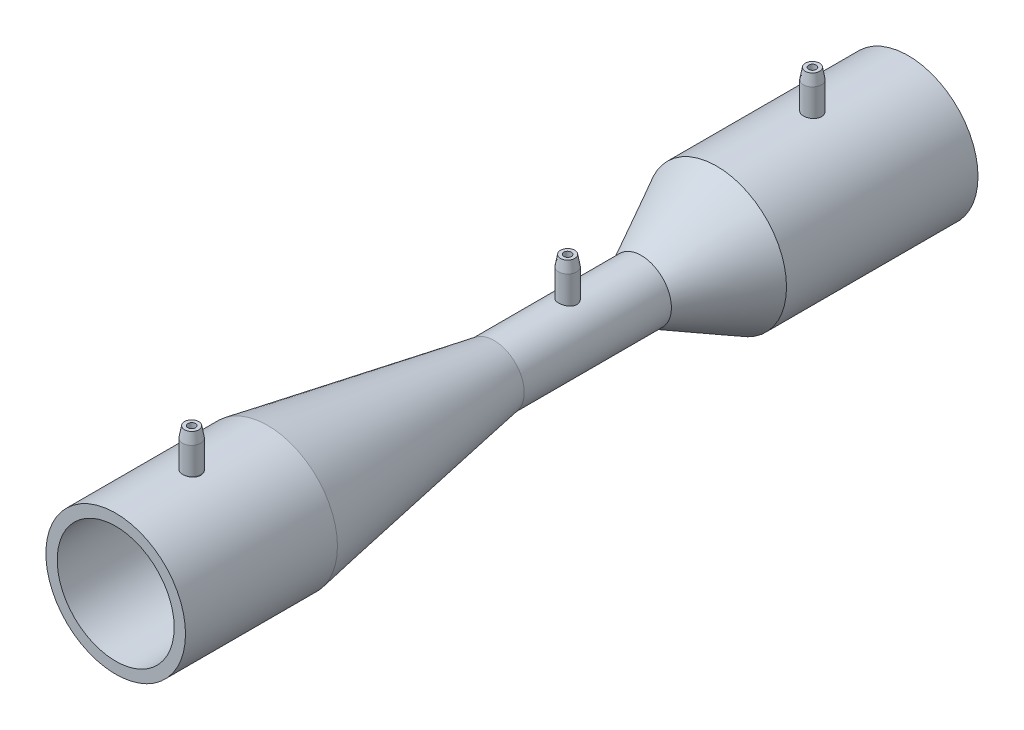
SolidWorks part; units mm, degrees
ref_plane "Front Plane" through (0, 0, 0) normal (0, 0, 1) x (1, 0, 0)
ref_plane "Top Plane" through (0, 0, 0) normal (0, 1, 0) x (1, 0, 0)
ref_plane "Right Plane" through (0, 0, 0) normal (1, 0, 0) x (0, 0, -1)
sketch "Sketch1" plane through (0, 0, 0) normal (1, 0, 0) x (0, 0, -1)
  line L0 (77.8723, 0) -> (-77.8723, 0) construction
  line L1 (-135.6286, 15.5) -> (77.8723, 15.5) construction
  line L2 (-135.6286, 15.5) -> (-95.6286, 15.5)
  line L3 (-95.6286, 15.5) -> (-35.6286, 5)
  line L4 (-35.6286, 5) -> (4.3714, 5)
  line L5 (4.3714, 5) -> (24.3714, 15.5)
  line L6 (24.3714, 15.5) -> (74.3714, 15.5)
  line L7 (-76.7205, 5) -> (45.4632, 5) construction
  line L8 (-135.6286, 18.5) -> (-95.3681, 18.5)
  line L9 (-95.3681, 18.5) -> (-35.3681, 8)
  line L10 (-35.3681, 8) -> (3.6317, 8)
  line L11 (3.6317, 8) -> (23.6317, 18.5)
  line L12 (23.6317, 18.5) -> (74.3714, 18.5)
  line L13 (-135.6286, 15.5) -> (-135.6286, 18.5)
  line L14 (74.3714, 15.5) -> (74.3714, 18.5)
  point P4 (0, 0)
  point P15 (-15.6286, 5)
  dimension "D1" = 15.5
  dimension "D2" = 40
  dimension "D3" = 60
  dimension "D4" = 40
  dimension "D5" = 20
  dimension "D6" = 50
  dimension "D7" = 15.5
  dimension "D8" = 5
  dimension "D9" = 3
revolve "Revolve1" add sketch "Sketch1" angle 360 about L0 reverse direction yes
sketch "Sketch2" plane through (0, 0, 0) normal (1, 0, 0) x (0, 0, -1)
  line L0 (-115.4984, 18.5) -> (-115.4984, 28.5)
  line L2 (-15.8682, 8) -> (-15.8682, 18)
  line L3 (-35.3681, 8) -> (3.6317, 8) construction
  line L4 (49.0016, 18.5) -> (49.0016, 28.5)
  line L5 (23.6317, 18.5) -> (74.3714, 18.5) construction
  line L6 (-95.3681, 18.5) -> (-135.6286, 18.5) construction
  line L7 (-14.8682, 5) -> (-14.8682, 18)
  line L8 (50.0016, 15.5) -> (50.0016, 28.5)
  line L9 (-114.4984, 18.5) -> (-114.4984, 28.5)
  line L10 (-16.8682, 5) -> (-16.8682, 18)
  line L11 (48.0016, 15.5) -> (48.0016, 28.5)
  line L13 (-13.4832, 5) -> (-13.4832, 18)
  line L14 (51.3866, 15.5) -> (51.3866, 28.5)
  line L16 (-18.2532, 5) -> (-18.2532, 18)
  line L17 (46.6166, 15.5) -> (46.6166, 28.5)
  line L19 (-18.2532, 18) -> (-13.4832, 18)
  line L20 (46.6166, 28.5) -> (51.3866, 28.5)
  line L25 (-135.6286, 15.5) -> (-95.6286, 15.5) construction
  line L26 (-116.4984, 18.5) -> (-116.4984, 28.5)
  line L27 (-113.1084, 18.5) -> (-113.1084, 28.5)
  line L28 (-117.8884, 18.5) -> (-117.8884, 28.5)
  line L29 (-18.2532, 8) -> (-18.2532, 18) construction
  line L30 (-35.6286, 5) -> (4.3714, 5) construction
  line L31 (-16.8682, 8) -> (-16.8682, 18) construction
  line L32 (-14.8682, 8) -> (-14.8682, 18) construction
  line L33 (-13.4832, 8) -> (-13.4832, 18) construction
  line L34 (46.6166, 18.5) -> (46.6166, 28.5) construction
  line L35 (24.3714, 15.5) -> (74.3714, 15.5) construction
  line L36 (48.0016, 18.5) -> (48.0016, 28.5) construction
  line L37 (50.0016, 18.5) -> (50.0016, 28.5) construction
  line L38 (51.3866, 18.5) -> (51.3866, 28.5) construction
  line L39 (46.6166, 15.5) -> (51.3866, 15.5)
  line L40 (-18.2532, 5) -> (-13.4832, 5)
  line L41 (-117.8834, 15.5) -> (-113.1134, 15.5)
  line L42 (-117.8884, 18.5) -> (-117.8834, 15.5)
  line L43 (-116.4984, 18.5) -> (-116.4984, 15.5)
  line L44 (-116.4984, 15.5) -> (-114.4984, 15.5)
  line L45 (-114.4984, 15.5) -> (-114.4984, 18.5)
  line L46 (-113.1134, 15.5) -> (-113.1084, 18.5)
  line L47 (-115.4984, 18.5) -> (-115.4984, 15.5)
  line L48 (-117.8884, 28.5) -> (-113.1084, 28.5)
  dimension "D2" = 10
  dimension "D3" = 10
  dimension "D1" = 10
  dimension "D4" = 1
  dimension "D6" = 2.39
  dimension "D7" = 2.39
revolve "Revolve2" add sketch "Sketch2" angle 360 about L0 region at (0, 22.0023, 113.8037)
revolve "Revolve3" add sketch "Sketch2<5>" angle 360 about L2 region at (0, 11.5, 14.1757)
sketch "Sketch2<5>" plane through (0, 0, 0) normal (1, 0, 0) x (0, 0, -1) same geometry as "Sketch2"
revolve "Revolve4" add sketch "Sketch2<6>" angle 360 about L4 region at (0, 22, -50.6941)
sketch "Sketch2<6>" plane through (0, 0, 0) normal (1, 0, 0) x (0, 0, -1) same geometry as "Sketch2"
chamfer "Chamfer1" distance 0.5 angle 80 1 edges at (0, 28.5, 113.1084) first distance on face at (0, 28.5, 113.1084)
chamfer "Chamfer2" distance 0.5 angle 80 1 edges at (0, 18, 13.4832) first distance on face at (0, 18, 13.4832)
chamfer "Chamfer3" distance 0.5 angle 80 1 edges at (0, 28.5, -51.3866) first distance on face at (0, 28.5, -51.3866)
sketch "Sketch4" plane through (0, 18, 0) normal (0, 1, 0) x (1, 0, 0)
  circle A0 centre (0, -15.8682) radius 1
  dimension "D1" = 2
extrude "Cut-Extrude2" cut sketch "Sketch4" against normal blind 15
sketch "Sketch5" plane through (0, 28.5, 0) normal (0, 1, 0) x (1, 0, 0)
  circle A0 centre (0, 49.0016) radius 1
  dimension "D1" = 2
extrude "Cut-Extrude3" cut sketch "Sketch5" against normal blind 15
sketch "Sketch6" plane through (0, 28.5, 0) normal (0, 1, 0) x (1, 0, 0)
  circle A0 centre (0, -115.4984) radius 1
extrude "Cut-Extrude4" cut sketch "Sketch6" against normal blind 30
move or copy body "Body-Convert to Mesh Body1" [suppressed] bodies to move or copy 109 copy no translate (0, 0, 0) parameters "D1"=0, "D2"=0, "D3"=0
equation "\"vacuum_attachment_radius\"= 15.5mm'Do not change"
equation "\"D1@Sketch1\"=\"vacuum_attachment_radius\""
equation "\"inlet_length\"= 40mm"
equation "\"inlet_decline_length\"= 60"
equation "\"D3@Sketch1\"=\"inlet_decline_length\""
equation "\"center_length\"= 40mm"
equation "\"D4@Sketch1\"=\"center_length\""
equation "\"outlet_incline_length\"= 20"
equation "\"D5@Sketch1\"=\"outlet_incline_length\""
equation "\"outlet_length\"= 50mm"
equation "\"D6@Sketch1\"=\"outlet_length\""
equation "\"outlet_radius\"= \"vacuum_attachment_radius\""
equation "\"center_radius\"= 5mm"
equation "\"D2@Sketch1\"=\"inlet_length\""
equation "\"D7@Sketch1\"=\"outlet_radius\""
equation "\"D8@Sketch1\"=\"center_radius\""
equation "\"nozzle_length\"=10"
equation "\"D2@Sketch2\"=\"nozzle_length\""
equation "\"D3@Sketch2\"=\"nozzle_length\""
